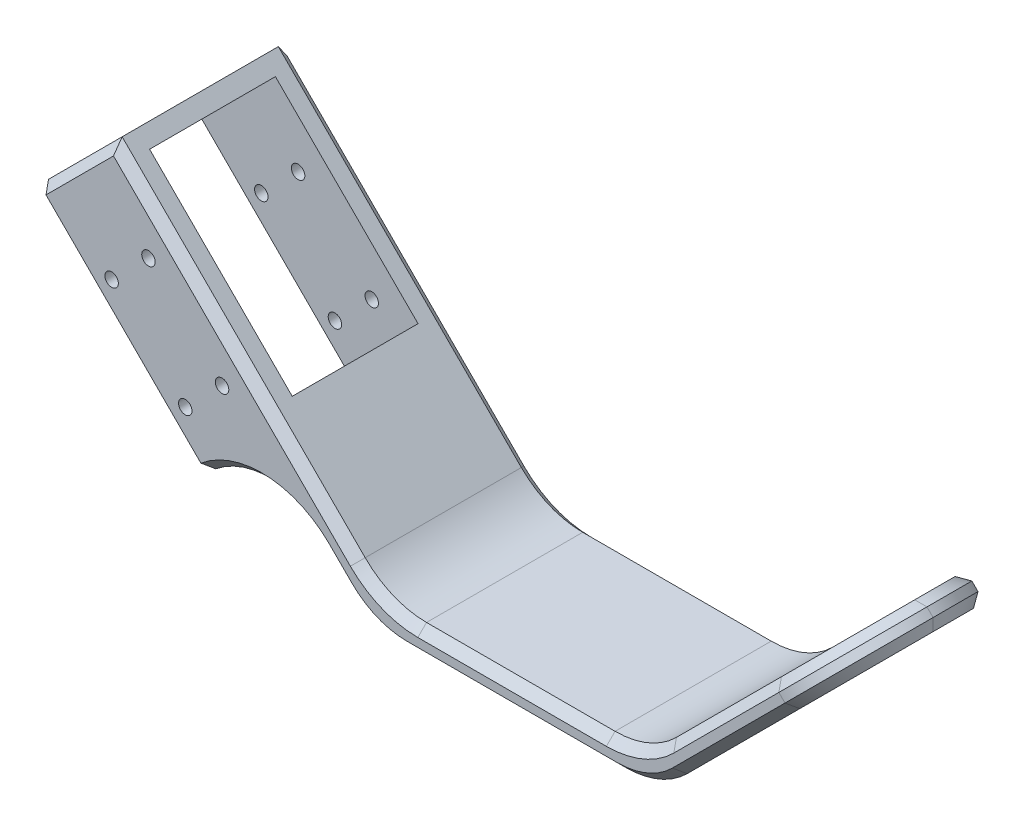
SolidWorks part; units mm, degrees
ref_plane "Front Plane" through (0, 0, 0) normal (0, 0, 1) x (1, 0, 0)
ref_plane "Top Plane" through (0, 0, 0) normal (0, 1, 0) x (1, 0, 0)
ref_plane "Right Plane" through (0, 0, 0) normal (1, 0, 0) x (0, 0, -1)
sketch "Sketch1" plane through (0, 0, 0) normal (0, 0, 1) x (1, 0, 0)
  line L0 (65, 0) -> (110.9619, 45.9619) construction
  line L1 (0, 0) -> (65, 0)
  line L2 (0, 0) -> (0, 6)
  line L3 (0, 6) -> (65, 6)
  line L4 (65, 0) -> (65, 6)
  line L5 (65, 0) -> (59, 6) construction
  line L6 (60.7574, 4.2426) -> (65, 0)
  line L7 (60.7574, 4.2426) -> (106.7193, 50.2046)
  line L8 (65, 0) -> (110.9619, 45.9619)
  line L9 (106.7193, 50.2046) -> (110.9619, 45.9619)
  line L10 (0, 0) -> (-63.6396, 63.6396) construction
  line L11 (0, 0) -> (6, 6) construction
  line L12 (4.2426, 4.2426) -> (0, 0)
  line L13 (4.2426, 4.2426) -> (-59.397, 67.8823)
  line L14 (0, 0) -> (-63.6396, 63.6396)
  line L15 (-59.397, 67.8823) -> (-63.6396, 63.6396)
  dimension "D1" = 65
  dimension "D2" = 6
  dimension "D3" = 45
  dimension "D4" = 6
  dimension "D5" = 65
  dimension "D6" = 90
  dimension "D7" = 6
  dimension "D8" = 45
  dimension "D9" = 90
  dimension "D10" = 90
extrude "Boss-Extrude1" add sketch "Sketch1" along normal blind 40 contours L13 L15 L14 L2 L3 | L12 L13 L3 L2 | L13 L12 L1 L6 L7 L3 | L7 L6 L4 L3 | L9 L7 L3 L4 L8 region at (32.5, 2.9415, 0) region at (-30.5855, 34.7997, 0) region at (1.5355, 3.7071, 0) region at (63.4645, 3.7071, 0) region at (86.75, 25.9529, 0)
sketch "Sketch2" plane through (28.2574, -28.2574, 0) normal (-0.7071, 0.7071, 0) x (0, 0, 1)
  line L0 (0, 110.9619) -> (40, 70.9619) construction
  line L1 (40, 48.4472) -> (40, 110.9619) construction
  line L2 (40, 110.9619) -> (0, 110.9619) construction
  circle A0 centre (20, 90.9619) radius 4
  circle A1 centre (20, 98.9619) radius 1.5
  circle A2 centre (28, 90.9619) radius 1.5
  circle A3 centre (20, 90.9619) radius 4
  circle A4 centre (20, 82.9619) radius 1.5
  circle A5 centre (20, 90.9619) radius 4
  circle A6 centre (12, 90.9619) radius 1.5
  circle A7 centre (20, 90.9619) radius 4
  point P21 (20, 90.9619)
  dimension "D1" = 3
  dimension "D2" = 8
  dimension "D4" = 45
  dimension "D5" = 0
  dimension "D3" = 4
extrude "Cut-Extrude1" cut sketch "Sketch2" against normal blind 40 contours A4 | A6 | A0 L0 | L0 A7 | A1 | A2 region at (93.426, 36.9113, 21.2004) region at (91.7283, 35.2136, 18.7996) region at (98.234, 41.7193, 20) region at (92.5772, 36.0624, 28) region at (86.9203, 30.4056, 20) region at (92.5772, 36.0624, 12)
sketch "Sketch3" plane through (0, 0, 0) normal (-0.7071, -0.7071, 0) x (0, 0, 1)
  line L0 (40, 0) -> (40, 90) construction
  line L1 (0, 90) -> (40, 90)
  line L2 (0, 90) -> (0, 35.5)
  line L3 (0, 35.5) -> (40, 35.5)
  line L4 (40, 90) -> (40, 35.5)
  line L5 (4, 86) -> (4, 39.5)
  line L6 (4, 39.5) -> (36, 39.5)
  line L7 (36, 86) -> (36, 39.5)
  line L8 (4, 86) -> (36, 86)
  line L9 (5.5, 86) -> (5.5, 39.5)
  line L10 (5.5, 86) -> (34.5, 86)
  line L11 (20, 86) -> (20, 39.5)
  line L12 (5.5, 39.5) -> (34.5, 39.5)
  line L13 (34.5, 86) -> (34.5, 39.5)
  line M13 (0, 90) -> (0, 0)
  line M15 (40, 0) -> (40, 90)
  line M16 (40, 90) -> (0, 90)
  dimension "D1" = 54.5
  dimension "D3" = 14.5
  dimension "D2" = 4
extrude "Boss-Extrude2" add sketch "Sketch3" along normal blind 18 contours L3 L5 L8 L10 L7 L6 M13 M15 M16 | L9 L8 L5 L6 | L8 L13 L6 L7 region at (-63.1616, 63.1616, 20) region at (-44.371, 44.371, 4.75) region at (-44.371, 44.371, 35.25)
sketch "Sketch4" plane through (0, 0, 0) normal (-0.7071, -0.7071, 0) x (0, 0, 1)
  line L4 (5.5, 86) -> (5.5, 39.5)
  line L5 (5.5, 39.5) -> (34.5, 39.5)
  line L6 (34.5, 39.5) -> (34.5, 86)
  line L7 (34.5, 86) -> (5.5, 86)
  line L8 (5.5, 86) -> (5.5, 39.5)
  line L9 (5.5, 39.5) -> (34.5, 39.5)
  line L10 (34.5, 39.5) -> (34.5, 86)
  line L11 (34.5, 86) -> (5.5, 86)
  dimension "D1" = 0
extrude "Cut-Extrude2" cut sketch "Sketch4" against normal blind 40
sketch "Sketch5" plane through (0, 0, 40) normal (0, 0, 1) x (1, 0, 0)
  circle A0 centre (-59.8212, 40.1637) radius 1.05 construction
  circle A1 centre (-42.8507, 23.1931) radius 1.05 construction
  circle A2 centre (-34.3654, 31.6784) radius 1.05 construction
  circle A3 centre (-51.336, 48.6489) radius 1.05 construction
  circle A4 centre (-59.8212, 40.1637) radius 1.05
  circle A5 centre (-42.8507, 23.1931) radius 1.05
  circle A6 centre (-34.3654, 31.6784) radius 1.05
  circle A7 centre (-51.336, 48.6489) radius 1.05
  circle A9 centre (-59.8212, 40.1637) radius 1.55
  circle A10 centre (-51.336, 48.6489) radius 1.55
  circle A11 centre (-51.336, 48.6489) radius 1.55
  circle A12 centre (-42.8507, 23.1931) radius 1.55
  circle A13 centre (-34.3654, 31.6784) radius 1.55
  dimension "D1" = 0.5
  dimension "D2" = 0.5
extrude "Cut-Extrude3" cut sketch "Sketch5" against normal through all both contours A11 A7 | A7 | A9 A4 | A4 | A13 A6 | A6 | A12 A5 | A5 region at (-59.8212, 40.1637, 40) region at (-42.8507, 23.1931, 40) region at (-34.3654, 31.6784, 40) region at (-51.336, 48.6489, 40) region at (-61.3274, 40.1637, 40) region at (-52.8421, 48.6489, 40) region at (-44.3568, 23.1931, 40) region at (-35.8715, 31.6784, 40)
fillet "Fillet1" radius 20 4 edges at (0, 0, 20) (2.4853, 6, 20) (62.5147, 6, 20) (65, 0, 20)
fillet "Fillet2" radius 20 1 edges at (-25.1023, 25.1023, 20)
fillet "Fillet3" radius 20 2 edges at (108.8406, 48.0833, 0) (108.8406, 48.0833, 40)
chamfer "Chamfer1" distance 2 angle 45 28 edges at (-67.8823, 59.397, 0) (-67.8823, 59.397, 40) (-24.1719, 16.8638, 0) (-8.4445, 8.4445, 0) (0.6306, 1.5224, 0) (32.5, 0, 0) (64.3694, 1.5224, 0) (83.8388, 18.8388, 0) (106.8198, 41.8198, 5.8579) (-24.1719, 16.8638, 40) (106.8198, 41.8198, 34.1421) (-8.4445, 8.4445, 40) (83.8388, 18.8388, 40) (0.6306, 1.5224, 40) (64.3694, 1.5224, 40) (32.5, 0, 40) (-31.3848, 39.8701, 0) (3.1159, 7.5224, 0) (32.5, 6, 0) (61.8841, 7.5224, 0) (80.4749, 23.9602, 0) (102.5772, 46.0624, 5.8579) (102.5772, 46.0624, 34.1421) (-31.3848, 39.8701, 40) (80.4749, 23.9602, 40) (3.1159, 7.5224, 40) (61.8841, 7.5224, 40) (32.5, 6, 40)
